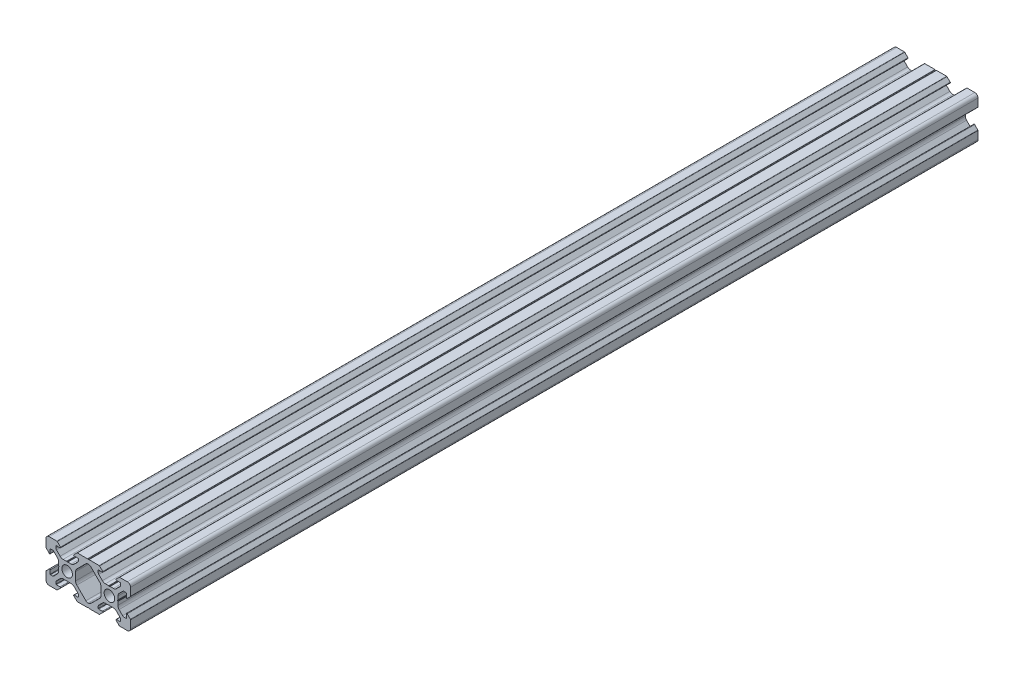
SolidWorks part; units mm, degrees
material "6063-T5"
ref_plane "Спереди" through (0, 0, 0) normal (0, 0, 1) x (1, 0, 0)
ref_plane "Сверху" through (0, 0, 0) normal (0, 1, 0) x (1, 0, 0)
ref_plane "Справа" through (0, 0, 0) normal (1, 0, 0) x (0, 0, -1)
sketch "Model" plane through (0, 0, 0) normal (0, 0, 1) x (1, 0, 0)
  line L0 (-5.4142, 2.9753) -> (-1.1373, 7.2523)
  line L1 (-6, -2.2365) -> (-6, 1.5611)
  line L2 (-5.4142, -3.6507) -> (-1.1373, -7.9276)
  line L3 (-0.1473, -8.3377) -> (0.1473, -8.3377)
  line L4 (5.4142, -3.6507) -> (1.1373, -7.9276)
  line L5 (6, -2.2365) -> (6, 1.5611)
  line L6 (5.4142, 2.9753) -> (1.1373, 7.2523)
  line L7 (-0.1473, 7.6623) -> (0.1473, 7.6623)
  line L8 (0.3757, 9.6623) -> (5.17, 9.6623)
  line L9 (5.3468, 9.5891) -> (6.8468, 8.0891)
  line L10 (6.67, 7.6623) -> (4.9, 7.6623)
  line L11 (4.7, 7.4623) -> (4.7, 6.6493)
  line L12 (4.9929, 5.9422) -> (6.687, 4.2481)
  line L13 (8.1012, 3.6623) -> (9.6623, 3.6623)
  line L14 (9.8185, 3.6075) -> (10, 3.4623)
  line L15 (10.1815, 3.6075) -> (10, 3.4623)
  line L16 (13.313, 4.2481) -> (15.0071, 5.9422)
  line L17 (15.3, 6.6493) -> (15.3, 7.4623)
  line L18 (15.1, 7.6623) -> (13.33, 7.6623)
  line L19 (14.6532, 9.5891) -> (13.1532, 8.0891)
  line L20 (14.83, 9.6623) -> (18.5, 9.6623)
  line L21 (20, 4.4923) -> (20, 8.1623)
  line L22 (19.9268, 4.3155) -> (18.4268, 2.8155)
  line L23 (18, 4.7623) -> (18, 2.9923)
  line L24 (16.987, 4.9623) -> (17.8, 4.9623)
  line L25 (14.5858, 2.9753) -> (16.2799, 4.6694)
  line L26 (14, 0) -> (14, 1.5611)
  line L27 (13.9452, -0.1562) -> (13.8, -0.3377)
  line L28 (13.9452, -0.5192) -> (13.8, -0.3377)
  line L29 (14, -0.6754) -> (14, -2.2365)
  line L30 (14.5858, -3.6507) -> (16.2799, -5.3448)
  line L31 (16.987, -5.6377) -> (17.8, -5.6377)
  line L32 (18, -5.4377) -> (18, -3.6677)
  line L33 (19.9268, -4.9909) -> (18.4268, -3.4909)
  line L34 (20, -5.1677) -> (20, -8.8377)
  line L35 (14.83, -10.3377) -> (18.5, -10.3377)
  line L36 (14.6532, -10.2645) -> (13.1532, -8.7645)
  line L37 (15.1, -8.3377) -> (13.33, -8.3377)
  line L38 (15.3, -7.3247) -> (15.3, -8.1377)
  line L39 (13.313, -4.9235) -> (15.0071, -6.6176)
  line L40 (10.3377, -4.3377) -> (11.8988, -4.3377)
  line L41 (10.1815, -4.2829) -> (10, -4.1377)
  line L42 (9.8185, -4.2829) -> (10, -4.1377)
  line L43 (8.1012, -4.3377) -> (9.6623, -4.3377)
  line L44 (4.9929, -6.6176) -> (6.687, -4.9235)
  line L45 (4.7, -8.1377) -> (4.7, -7.3247)
  line L46 (6.67, -8.3377) -> (4.9, -8.3377)
  line L47 (5.3468, -10.2645) -> (6.8468, -8.7645)
  line L48 (0.3757, -10.3377) -> (5.17, -10.3377)
  line L49 (0, -10.1377) -> (0.237, -10.2957)
  line L50 (0, -10.1377) -> (-0.237, -10.2957)
  line L51 (-0.3757, -10.3377) -> (-5.17, -10.3377)
  line L52 (-5.3468, -10.2645) -> (-6.8468, -8.7645)
  line L53 (-6.67, -8.3377) -> (-4.9, -8.3377)
  line L54 (-4.7, -8.1377) -> (-4.7, -7.3247)
  line L55 (-4.9929, -6.6176) -> (-6.687, -4.9235)
  line L56 (-8.1012, -4.3377) -> (-9.6623, -4.3377)
  line L57 (-9.8185, -4.2829) -> (-10, -4.1377)
  line L58 (-10.1815, -4.2829) -> (-10, -4.1377)
  line L59 (-10.3377, -4.3377) -> (-11.8988, -4.3377)
  line L60 (-13.313, -4.9235) -> (-15.0071, -6.6176)
  line L61 (-15.3, -7.3247) -> (-15.3, -8.1377)
  line L62 (-15.1, -8.3377) -> (-13.33, -8.3377)
  line L63 (-14.6532, -10.2645) -> (-13.1532, -8.7645)
  line L64 (-14.83, -10.3377) -> (-18.5, -10.3377)
  line L65 (-20, -5.1677) -> (-20, -8.8377)
  line L66 (-19.9268, -4.9909) -> (-18.4268, -3.4909)
  line L67 (-18, -5.4377) -> (-18, -3.6677)
  line L68 (-16.987, -5.6377) -> (-17.8, -5.6377)
  line L69 (-14.5858, -3.6507) -> (-16.2799, -5.3448)
  line L70 (-14, -0.6754) -> (-14, -2.2365)
  line L71 (-13.9452, -0.5192) -> (-13.8, -0.3377)
  line L72 (-13.9452, -0.1562) -> (-13.8, -0.3377)
  line L73 (-14, 0) -> (-14, 1.5611)
  line L74 (-14.5858, 2.9753) -> (-16.2799, 4.6694)
  line L75 (-16.987, 4.9623) -> (-17.8, 4.9623)
  line L76 (-18, 4.7623) -> (-18, 2.9923)
  line L77 (-19.9268, 4.3155) -> (-18.4268, 2.8155)
  line L78 (-20, 4.4923) -> (-20, 8.1623)
  line L79 (-14.6532, 9.5891) -> (-13.1532, 8.0891)
  line L80 (-10.1815, 3.6075) -> (-10, 3.4623)
  line L81 (-9.8185, 3.6075) -> (-10, 3.4623)
  line L82 (-8.1012, 3.6623) -> (-9.6623, 3.6623)
  line L83 (-4.9929, 5.9422) -> (-6.687, 4.2481)
  line L84 (-4.7, 7.4623) -> (-4.7, 6.6493)
  line L85 (-6.67, 7.6623) -> (-4.9, 7.6623)
  line L86 (-5.3468, 9.5891) -> (-6.8468, 8.0891)
  line L87 (-0.3757, 9.6623) -> (-5.17, 9.6623)
  line L88 (0, 9.4623) -> (-0.237, 9.6203)
  line L89 (0, 9.4623) -> (0.237, 9.6203)
  line L90 (10.3377, 3.6623) -> (11.8988, 3.6623)
  line L91 (-10.3377, 3.6623) -> (-11.8988, 3.6623)
  line L92 (-13.313, 4.2481) -> (-15.0071, 5.9422)
  line L93 (-15.3, 6.6493) -> (-15.3, 7.4623)
  line L94 (-15.1, 7.6623) -> (-13.33, 7.6623)
  line L95 (-14.83, 9.6623) -> (-18.5, 9.6623)
  circle A0 centre (10, -0.3377) radius 2.5
  arc A1 (-0.1473, 7.6623) -> (-1.1373, 7.2523) centre (-0.1473, 6.2623) ccw
  arc A2 (-5.4142, 2.9753) -> (-6, 1.5611) centre (-4, 1.5611) ccw
  arc A3 (-6, -2.2365) -> (-5.4142, -3.6507) centre (-4, -2.2365) ccw
  arc A4 (-1.1373, -7.9276) -> (-0.1473, -8.3377) centre (-0.1473, -6.9377) ccw
  arc A5 (0.1473, -8.3377) -> (1.1373, -7.9276) centre (0.1473, -6.9377) ccw
  arc A6 (5.4142, -3.6507) -> (6, -2.2365) centre (4, -2.2365) ccw
  arc A7 (6, 1.5611) -> (5.4142, 2.9753) centre (4, 1.5611) ccw
  arc A8 (1.1373, 7.2523) -> (0.1473, 7.6623) centre (0.1473, 6.2623) ccw
  arc A9 (0.3757, 9.6623) -> (0.237, 9.6203) centre (0.3757, 9.4123) ccw
  arc A10 (5.3468, 9.5891) -> (5.17, 9.6623) centre (5.17, 9.4123) ccw
  arc A11 (6.67, 7.6623) -> (6.8468, 8.0891) centre (6.67, 7.9123) ccw
  arc A12 (4.9, 7.6623) -> (4.7, 7.4623) centre (4.9, 7.4623) ccw
  arc A13 (4.7, 6.6493) -> (4.9929, 5.9422) centre (5.7, 6.6493) ccw
  arc A14 (6.687, 4.2481) -> (8.1012, 3.6623) centre (8.1012, 5.6623) ccw
  arc A15 (9.8185, 3.6075) -> (9.6623, 3.6623) centre (9.6623, 3.4123) ccw
  arc A16 (10.3377, 3.6623) -> (10.1815, 3.6075) centre (10.3377, 3.4123) ccw
  arc A17 (11.8988, 3.6623) -> (13.313, 4.2481) centre (11.8988, 5.6623) ccw
  arc A18 (15.0071, 5.9422) -> (15.3, 6.6493) centre (14.3, 6.6493) ccw
  arc A19 (15.3, 7.4623) -> (15.1, 7.6623) centre (15.1, 7.4623) ccw
  arc A20 (13.1532, 8.0891) -> (13.33, 7.6623) centre (13.33, 7.9123) ccw
  arc A21 (14.83, 9.6623) -> (14.6532, 9.5891) centre (14.83, 9.4123) ccw
  arc A22 (20, 8.1623) -> (18.5, 9.6623) centre (18.5, 8.1623) ccw
  arc A23 (19.9268, 4.3155) -> (20, 4.4923) centre (19.75, 4.4923) ccw
  arc A24 (18, 2.9923) -> (18.4268, 2.8155) centre (18.25, 2.9923) ccw
  arc A25 (18, 4.7623) -> (17.8, 4.9623) centre (17.8, 4.7623) ccw
  arc A26 (16.987, 4.9623) -> (16.2799, 4.6694) centre (16.987, 3.9623) ccw
  arc A27 (14.5858, 2.9753) -> (14, 1.5611) centre (16, 1.5611) ccw
  arc A28 (13.9452, -0.1562) -> (14, 0) centre (13.75, 0) ccw
  arc A29 (14, -0.6754) -> (13.9452, -0.5192) centre (13.75, -0.6754) ccw
  arc A30 (14, -2.2365) -> (14.5858, -3.6507) centre (16, -2.2365) ccw
  arc A31 (16.2799, -5.3448) -> (16.987, -5.6377) centre (16.987, -4.6377) ccw
  arc A32 (17.8, -5.6377) -> (18, -5.4377) centre (17.8, -5.4377) ccw
  arc A33 (18.4268, -3.4909) -> (18, -3.6677) centre (18.25, -3.6677) ccw
  arc A34 (20, -5.1677) -> (19.9268, -4.9909) centre (19.75, -5.1677) ccw
  arc A35 (18.5, -10.3377) -> (20, -8.8377) centre (18.5, -8.8377) ccw
  arc A36 (14.6532, -10.2645) -> (14.83, -10.3377) centre (14.83, -10.0877) ccw
  arc A37 (13.33, -8.3377) -> (13.1532, -8.7645) centre (13.33, -8.5877) ccw
  arc A38 (15.1, -8.3377) -> (15.3, -8.1377) centre (15.1, -8.1377) ccw
  arc A39 (15.3, -7.3247) -> (15.0071, -6.6176) centre (14.3, -7.3247) ccw
  arc A40 (13.313, -4.9235) -> (11.8988, -4.3377) centre (11.8988, -6.3377) ccw
  arc A41 (10.1815, -4.2829) -> (10.3377, -4.3377) centre (10.3377, -4.0877) ccw
  arc A42 (9.6623, -4.3377) -> (9.8185, -4.2829) centre (9.6623, -4.0877) ccw
  arc A43 (8.1012, -4.3377) -> (6.687, -4.9235) centre (8.1012, -6.3377) ccw
  arc A44 (4.9929, -6.6176) -> (4.7, -7.3247) centre (5.7, -7.3247) ccw
  arc A45 (4.7, -8.1377) -> (4.9, -8.3377) centre (4.9, -8.1377) ccw
  arc A46 (6.8468, -8.7645) -> (6.67, -8.3377) centre (6.67, -8.5877) ccw
  arc A47 (5.17, -10.3377) -> (5.3468, -10.2645) centre (5.17, -10.0877) ccw
  arc A48 (0.237, -10.2957) -> (0.3757, -10.3377) centre (0.3757, -10.0877) ccw
  arc A49 (-0.3757, -10.3377) -> (-0.237, -10.2957) centre (-0.3757, -10.0877) ccw
  arc A50 (-5.3468, -10.2645) -> (-5.17, -10.3377) centre (-5.17, -10.0877) ccw
  arc A51 (-6.67, -8.3377) -> (-6.8468, -8.7645) centre (-6.67, -8.5877) ccw
  arc A52 (-4.9, -8.3377) -> (-4.7, -8.1377) centre (-4.9, -8.1377) ccw
  arc A53 (-4.7, -7.3247) -> (-4.9929, -6.6176) centre (-5.7, -7.3247) ccw
  arc A54 (-6.687, -4.9235) -> (-8.1012, -4.3377) centre (-8.1012, -6.3377) ccw
  arc A55 (-9.8185, -4.2829) -> (-9.6623, -4.3377) centre (-9.6623, -4.0877) ccw
  arc A56 (-10.3377, -4.3377) -> (-10.1815, -4.2829) centre (-10.3377, -4.0877) ccw
  arc A57 (-11.8988, -4.3377) -> (-13.313, -4.9235) centre (-11.8988, -6.3377) ccw
  arc A58 (-15.0071, -6.6176) -> (-15.3, -7.3247) centre (-14.3, -7.3247) ccw
  arc A59 (-15.3, -8.1377) -> (-15.1, -8.3377) centre (-15.1, -8.1377) ccw
  arc A60 (-13.1532, -8.7645) -> (-13.33, -8.3377) centre (-13.33, -8.5877) ccw
  arc A61 (-14.83, -10.3377) -> (-14.6532, -10.2645) centre (-14.83, -10.0877) ccw
  arc A62 (-20, -8.8377) -> (-18.5, -10.3377) centre (-18.5, -8.8377) ccw
  arc A63 (-19.9268, -4.9909) -> (-20, -5.1677) centre (-19.75, -5.1677) ccw
  arc A64 (-18, -3.6677) -> (-18.4268, -3.4909) centre (-18.25, -3.6677) ccw
  arc A65 (-18, -5.4377) -> (-17.8, -5.6377) centre (-17.8, -5.4377) ccw
  arc A66 (-16.987, -5.6377) -> (-16.2799, -5.3448) centre (-16.987, -4.6377) ccw
  arc A67 (-14.5858, -3.6507) -> (-14, -2.2365) centre (-16, -2.2365) ccw
  arc A68 (-13.9452, -0.5192) -> (-14, -0.6754) centre (-13.75, -0.6754) ccw
  arc A69 (-14, 0) -> (-13.9452, -0.1562) centre (-13.75, 0) ccw
  arc A70 (-14, 1.5611) -> (-14.5858, 2.9753) centre (-16, 1.5611) ccw
  arc A71 (-16.2799, 4.6694) -> (-16.987, 4.9623) centre (-16.987, 3.9623) ccw
  arc A72 (-17.8, 4.9623) -> (-18, 4.7623) centre (-17.8, 4.7623) ccw
  arc A73 (-18.4268, 2.8155) -> (-18, 2.9923) centre (-18.25, 2.9923) ccw
  arc A74 (-20, 4.4923) -> (-19.9268, 4.3155) centre (-19.75, 4.4923) ccw
  arc A75 (-18.5, 9.6623) -> (-20, 8.1623) centre (-18.5, 8.1623) ccw
  arc A76 (-14.6532, 9.5891) -> (-14.83, 9.6623) centre (-14.83, 9.4123) ccw
  arc A77 (-13.33, 7.6623) -> (-13.1532, 8.0891) centre (-13.33, 7.9123) ccw
  arc A78 (-15.1, 7.6623) -> (-15.3, 7.4623) centre (-15.1, 7.4623) ccw
  arc A79 (-15.3, 6.6493) -> (-15.0071, 5.9422) centre (-14.3, 6.6493) ccw
  arc A80 (-13.313, 4.2481) -> (-11.8988, 3.6623) centre (-11.8988, 5.6623) ccw
  arc A81 (-10.1815, 3.6075) -> (-10.3377, 3.6623) centre (-10.3377, 3.4123) ccw
  arc A82 (-9.6623, 3.6623) -> (-9.8185, 3.6075) centre (-9.6623, 3.4123) ccw
  arc A83 (-8.1012, 3.6623) -> (-6.687, 4.2481) centre (-8.1012, 5.6623) ccw
  arc A84 (-4.9929, 5.9422) -> (-4.7, 6.6493) centre (-5.7, 6.6493) ccw
  arc A85 (-4.7, 7.4623) -> (-4.9, 7.6623) centre (-4.9, 7.4623) ccw
  arc A86 (-6.8468, 8.0891) -> (-6.67, 7.6623) centre (-6.67, 7.9123) ccw
  arc A87 (-5.17, 9.6623) -> (-5.3468, 9.5891) centre (-5.17, 9.4123) ccw
  arc A88 (-0.237, 9.6203) -> (-0.3757, 9.6623) centre (-0.3757, 9.4123) ccw
  circle A89 centre (-10, -0.3377) radius 2.5
  dimension "D1" = 20
  dimension "D2" = 40
  dimension "D3" = 20
extrude "Body" add sketch "Model" along normal blind 401
hole_wizard "Tap Drill for M6x1.0 Tap1" positions "Sketch4" profile "Sketch5" hole size "M6x1.0" standard "ANSI Metric"
sketch "Sketch4" plane through (0, 0, 401) normal (0, 0, 1) x (1, 0, 0)
  point P0 (-10, -0.3377)
  point P3 (10, -0.3377)
  point P8 (-10, -0.3377)
  point P10 (10, -0.3377)
  point P16 (10, -0.3377)
  point P18 (-10, -0.3377)
  point P25 (0, 0)
  point P26 (0, 0)
sketch "Sketch5" plane through (-10, -0.3377, 401) normal (1, 0, 0) x (0, -1, 0)
  line L0 (0, 0) -> (0, 15)
  line L1 (0, 15) -> (2.5, 13.4978)
  line L2 (2.5, 13.4978) -> (2.5, 0)
  line L5 (2.5, 0) -> (0, 0)
  line L10 (0, 15) -> (-2.5, 13.4978) construction
  line L11 (0, -6.35) -> (0, 107.95) construction
  dimension "Hole Dia." = 5
  dimension "Hole Depth" = 15
  dimension "Drill Angle" = 118
hole_wizard "Tap Drill for M6x1.0 Tap2" positions "Sketch6" profile "Sketch7" hole size "M6x1.0" standard "ANSI Metric"
sketch "Sketch6" plane through (0, 0, 0) normal (0, 0, -1) x (-1, 0, 0)
  point P0 (-10, -0.3377)
  point P3 (10, -0.3377)
sketch "Sketch7" plane through (10, -0.3377, 0) normal (1, 0, 0) x (0, 1, 0)
  line L0 (0, 0) -> (0, 15)
  line L1 (0, 15) -> (2.5, 13.4978)
  line L2 (2.5, 13.4978) -> (2.5, 0)
  line L5 (2.5, 0) -> (0, 0)
  line L10 (0, 15) -> (-2.5, 13.4978) construction
  line L11 (0, -6.35) -> (0, 107.95) construction
  dimension "Hole Dia." = 5
  dimension "Hole Depth" = 15
  dimension "Drill Angle" = 118
